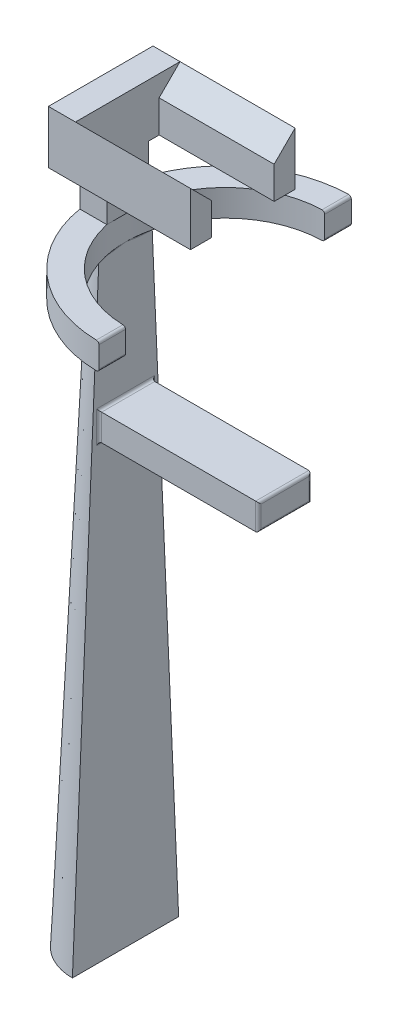
SolidWorks part; units mm, degrees
ref_plane "Front Plane" through (0, 0, 0) normal (0, 0, 1) x (1, 0, 0)
ref_plane "Top Plane" through (0, 0, 0) normal (0, 1, 0) x (1, 0, 0)
ref_plane "Right Plane" through (0, 0, 0) normal (1, 0, 0) x (0, 0, -1)
sketch "Sketch1" plane through (0, 0, 0) normal (0, 1, 0) x (0, 0, -1)
  line L0 (-120.65, 0) -> (120.65, 0)
  arc A0 (95.25, 0) -> (-95.25, 0) centre (0, 0) ccw
  arc A1 (120.65, 0) -> (-120.65, 0) centre (0, 0) ccw
  dimension "D1" = 190.5
  dimension "D2" = 241.3
extrude "Boss-Extrude1" add sketch "Sketch1" along normal blind 25.4 contours L0 A1 A0 region at (-117.9522, 0, 0)
sketch "Sketch4" plane through (0, 0, 0) normal (0, 0, 1) x (1, 0, 0)
  line L0 (-95.25, 0) -> (-120.65, 0)
  line L2 (-146.05, -584.2) -> (-95.25, -584.2)
  line L4 (-95.25, 0) -> (-95.25, -584.2)
  line L5 (-120.65, 0) -> (-146.05, -584.2)
  dimension "D1" = 50.8
  dimension "D2" = 584.2
revolve "Revolve1" add sketch "Sketch4" angle 180 mid plane about L4
sketch "Sketch5" plane through (-95.25, 0, 0) normal (1, 0, 0) x (0, 0, -1)
  line L0 (-95.25, 0) -> (0, 0) construction
  line L1 (-25.4, -127) -> (25.4, -127)
  line L2 (-25.4, -127) -> (-25.4, -152.4)
  line L3 (-25.4, -152.4) -> (25.4, -152.4)
  line L4 (25.4, -127) -> (25.4, -152.4)
  point P7 (0, -127)
  dimension "D1" = 127
  dimension "D2" = 50.8
  dimension "D3" = 25.4
extrude "Boss-Extrude3" add sketch "Sketch5" along normal blind 152.4
fillet "Fillet1" radius 2.54 4 edges at (-95.25, -152.4, 0) (-95.25, -139.7, -25.4) (-95.25, -139.7, 25.4) (-95.25, -127, 0)
fillet "Fillet2" radius 2.54 4 edges at (57.15, -139.7, -25.4) (57.15, -152.4, 0) (57.15, -139.7, 25.4) (57.15, -127, 0)
fillet "Fillet5" radius 2.54 2 edges at (-95.25, 0, 12.7) (-95.25, 0, -12.7)
fillet "Fillet6" radius 2.54 4 edges at (0, 0, -107.95) (0, 25.4, -107.95) (0, 0, 107.95) (0, 25.4, 107.95)
sketch "Sketch6" plane through (0, 25.4, 0) normal (0, 1, 0) x (1, 0, 0)
  line L0 (-120.65, 0) -> (54.61, 0) construction
  line L1 (54.61, -25.4) -> (54.61, 25.4) construction
  line L3 (-118.9808, 20) -> (-93.1266, 20)
  line L4 (-118.9808, 20) -> (-118.9808, -20)
  line L5 (-118.9808, -20) -> (-93.1266, -20)
  line L6 (-93.1266, 20) -> (-93.1266, -20)
  arc A0 (-2.54, 120.6233) -> (-2.54, -120.6233) centre (0, 0) ccw construction
  arc A1 (-2.54, 95.2161) -> (-2.54, -95.2161) centre (0, 0) ccw construction
  dimension "D1" = 20
  dimension "D2" = 20
extrude "Boss-Extrude4" add sketch "Sketch6" along normal blind 100
sketch "Sketch8" plane through (0, 0, -20) normal (0, 0, -1) x (-1, 0, 0)
  line L0 (118.9808, 125.4) -> (118.9808, 25.4) construction
  line L1 (93.1266, 125.4) -> (118.9808, 125.4)
  line L2 (93.1266, 125.4) -> (93.1266, 74.6)
  line L3 (93.1266, 74.6) -> (118.9808, 74.6)
  line L4 (118.9808, 125.4) -> (118.9808, 74.6)
  dimension "D1" = 50.8
extrude "Boss-Extrude5" add sketch "Sketch8" along normal blind 30.0101
sketch "Sketch9" plane through (0, 0, 20) normal (0, 0, 1) x (1, 0, 0)
  line L0 (-93.1266, 125.4) -> (-93.1266, 25.4) construction
  line L1 (-118.9808, 125.4) -> (-93.1266, 125.4)
  line L2 (-118.9808, 125.4) -> (-118.9808, 74.6)
  line L3 (-118.9808, 74.6) -> (-93.1266, 74.6)
  line L4 (-93.1266, 125.4) -> (-93.1266, 74.6)
  dimension "D1" = 50.8
extrude "Boss-Extrude6" add sketch "Sketch9" along normal blind 30.0101
sketch "Sketch11" plane through (-93.1266, 0, 0) normal (1, 0, 0) x (0, 0, -1)
  line L0 (30.0101, 105.4) -> (30.0101, 74.6)
  line L7 (50.0101, 125.4) -> (30.0101, 105.4)
  line L8 (50.0101, 74.6) -> (20, 74.6) construction
  line L9 (30.0101, 74.6) -> (50.0101, 74.6)
  line L10 (50.0101, 74.6) -> (50.0101, 125.4)
extrude "Boss-Extrude7" add sketch "Sketch11" along normal blind 110
sketch "Sketch12" plane through (-93.1266, 0, 0) normal (1, 0, 0) x (0, 0, -1)
  line L0 (-30.0101, 105.4) -> (-30.0101, 74.6)
  line L7 (-50.0101, 125.4) -> (-30.0101, 105.4)
  line L8 (-50.0101, 74.6) -> (-20, 74.6) construction
  line L9 (-30.0101, 74.6) -> (-50.0101, 74.6)
  line L10 (-50.0101, 74.6) -> (-50.0101, 125.4)
extrude "Boss-Extrude8" add sketch "Sketch12" along normal blind 110
